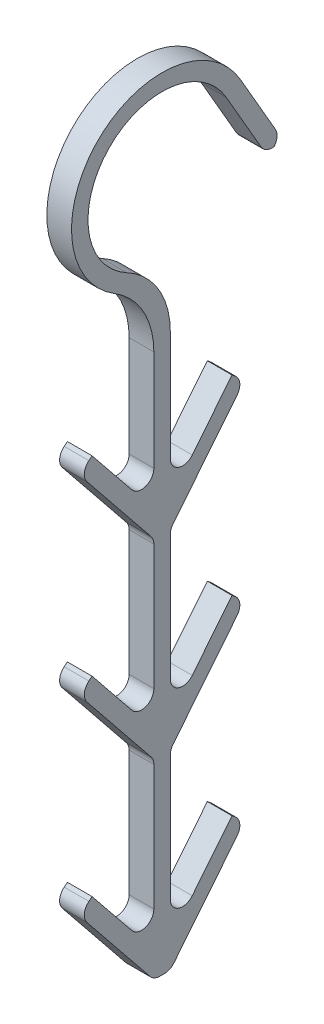
SolidWorks part; units mm, degrees
ref_plane "Front Plane" through (0, 0, 0) normal (0, 0, 1) x (1, 0, 0)
ref_plane "Top Plane" through (0, 0, 0) normal (0, 1, 0) x (1, 0, 0)
ref_plane "Right Plane" through (0, 0, 0) normal (1, 0, 0) x (0, 0, -1)
sketch "Sketch1" plane through (0, 0, 0) normal (1, 0, 0) x (0, 0, -1)
  circle A2 centre (0, 0) radius 22
  circle A3 centre (0, 0) radius 18
  dimension "D1" = 44
  dimension "D2" = 4
extrude "Boss-Extrude1" add sketch "Sketch1" along normal blind 6
sketch "Sketch2" plane through (6, 0, 0) normal (1, 0, 0) x (0, 0, -1)
  line L0 (19.0526, 11) -> (29.0526, -6.3205)
  line L1 (29.0526, -6.3205) -> (25.5885, -8.3205)
  line L2 (25.5885, -8.3205) -> (15.5885, 9)
  line L3 (15.5885, 9) -> (19.0526, 11)
  line L4 (0, 0) -> (0, 18) construction
  circle A0 centre (0, 0) radius 22 construction
  circle A1 centre (0, 0) radius 18 construction
  dimension "D1" = 20
  dimension "D2" = 30
extrude "Boss-Extrude2" add sketch "Sketch2" against normal up to surface (6 mm away) up to face at (0, 0, -22)
sketch "Sketch3" plane through (6, 0, 0) normal (1, 0, 0) x (0, 0, -1)
  line L0 (4.6587, -17.3867) -> (5.694, -21.2504)
  line L1 (0, 0) -> (0, -22) construction
  line L2 (21.913, -1.9545) -> (15.5885, 9)
  line L3 (21.913, -1.9545) -> (25.5885, -8.3205) construction
  circle A0 centre (0, 0) radius 18
  circle A1 centre (0, 0) radius 22
  circle A2 centre (0, 0) radius 18 construction
  arc A3 (19.0526, 11) -> (21.913, -1.9545) centre (0, 0) ccw construction
  circle M6 centre (0, 0) radius 18
  arc M8 (19.0526, 11) -> (21.913, -1.9545) centre (0, 0) ccw
  dimension "D1" = 15
extrude "Cut-Extrude1" cut sketch "Sketch3" against normal through all contours L2 L0 M8 M6 region at (6, -10.4169, -15.0287)
sketch "Sketch4" plane through (6, 0, 0) normal (1, 0, 0) x (0, 0, -1)
  line L1 (-2, -17.8885) -> (2, -17.8885)
  line L2 (-2, -17.8885) -> (-2, -47.8885)
  line L3 (-2, -47.8885) -> (2, -47.8885)
  line L4 (2, -17.8885) -> (2, -47.8885)
  arc A0 (15.5885, 9) -> (4.6587, -17.3867) centre (0, 0) ccw construction
  point P7 (0, -17.8885)
  dimension "D1" = 4
  dimension "D2" = 30
extrude "Boss-Extrude3" add sketch "Sketch4" against normal up to surface (6 mm away) up to face at (0, -1.442, -6.6971)
sketch "Sketch5" plane through (6, 0, 0) normal (1, 0, 0) x (0, 0, -1)
  line L0 (2, -21.9089) -> (2, -17.8885)
  line L1 (2, -17.8885) -> (4.6587, -17.3867)
  line L2 (4.6587, -17.3867) -> (5.694, -21.2504)
  arc A0 (2, -21.9089) -> (5.694, -21.2504) centre (2, -11.2189) ccw
extrude "Cut-Extrude2" cut sketch "Sketch5" against normal through all
fillet "Fillet1" radius 20 2 edges at (3, -17.8885, -2) (3, -21.9089, 2)
fillet "Fillet2" radius 20 1 edges at (3, -17.8885, 2)
sketch "Sketch6" plane through (0, 0, 0) normal (-1, 0, 0) x (0, 0, 1)
  line L0 (-2, -47.8885) -> (2, -47.8885) construction
  line L1 (-2, -47.8885) -> (2, -47.8885)
  line L2 (-2, -47.8885) -> (-2, -167.8885)
  line L3 (-2, -167.8885) -> (2, -167.8885)
  line L4 (2, -47.8885) -> (2, -167.8885)
  point P4 (0, -47.8885)
  point P7 (0, -47.8885)
  dimension "D1" = 120
  dimension "D2" = 4
extrude "Boss-Extrude4" add sketch "Sketch6" against normal up to surface (6 mm away) up to face at (6, -15.5959, -3.8329)
sketch "Sketch7" plane through (0, 0, -2) normal (1, 0, 0) x (0, 0, -1)
  line L0 (-4, -167.8885) -> (-22.1152, -145.3977)
  line L1 (-4, -167.8885) -> (-4, -35.7771) construction
  line L2 (-22.1152, -145.3977) -> (-19, -142.8885)
  line L3 (-19, -142.8885) -> (-4, -161.5118)
  line L4 (-4, -161.5118) -> (-4, -167.8885)
  line L5 (-4, -115.135) -> (-4, -121.5118)
  line L6 (-4, -121.5118) -> (-22.1152, -99.0209)
  line L7 (-22.1152, -99.0209) -> (-19, -96.5118)
  line L8 (-19, -96.5118) -> (-4, -115.135)
  line L9 (-4, -68.7583) -> (-4, -75.135)
  line L10 (-4, -75.135) -> (-22.1152, -52.6441)
  line L11 (-22.1152, -52.6441) -> (-19, -50.135)
  line L12 (-19, -50.135) -> (-4, -68.7583)
  line L17 (-4, -22.3815) -> (-4, -28.7583) [skipped]
  line L18 (-4, -28.7583) -> (-22.1152, -6.2674) [skipped]
  line L19 (-22.1152, -6.2674) -> (-19, -3.7583) [skipped]
  line L20 (-19, -3.7583) -> (-4, -22.3815) [skipped]
  dimension "D1" = 4
  dimension "D2" = 15
  dimension "D3" = 25
  dimension "D5" = 40
  dimension "D4" = 4
extrude "Boss-Extrude5" add sketch "Sketch7" along normal blind 6
mirror "Mirror1" about plane through (0, 0, 0) normal (0, 0, 1) of "Boss-Extrude5"
fillet "Fillet3" radius 3 20 edges at (3, -52.6441, 20.1152) (3, -99.0209, 20.1152) (3, -145.3977, 20.1152) (3, -167.8885, 2) (3, -75.135, 2) (3, -121.5118, 2) (3, -68.7583, 2) (3, -115.135, 2) (3, -161.5118, 2) (3, -6.3205, -29.0526) (3, -8.3205, -25.5885) (3, -68.7583, -2) (3, -115.135, -2) (3, -161.5118, -2) (3, -75.135, -2) (3, -121.5118, -2) (3, -167.8885, -2) (3, -145.3977, -20.1152) (3, -99.0209, -20.1152) (3, -52.6441, -20.1152)
